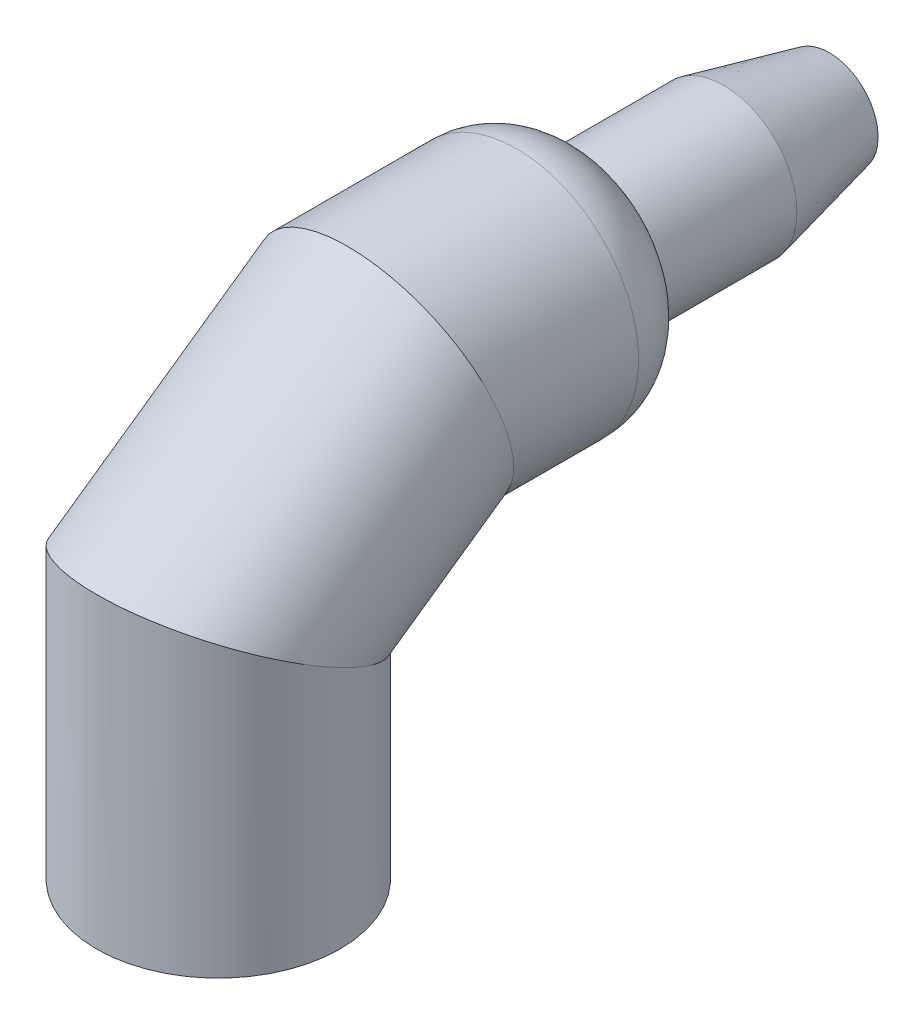
SolidWorks part; units mm, degrees
material "ABS"
ref_plane "Front Plane" through (0, 0, 0) normal (0, 0, 1) x (1, 0, 0)
ref_plane "Top Plane" through (0, 0, 0) normal (0, 1, 0) x (1, 0, 0)
ref_plane "Right Plane" through (0, 0, 0) normal (1, 0, 0) x (0, 0, -1)
sketch "Sketch1" plane through (0, 0, 0) normal (0, 1, 0) x (1, 0, 0)
  circle A0 centre (0, 0) radius 4.1
  circle A1 centre (0, 0) radius 5.1
  dimension "D1" = 8.2
  dimension "D2" = 1
sketch "Sketch2" plane through (0, 0, 0) normal (1, 0, 0) x (0, 0, -1)
  line L0 (5.1, 5) -> (7.4382, 6.6372)
  line L1 (-5.1, 5) -> (-1.6582, 7.41)
  line L3 (-1.6582, 7.41) -> (7.4382, 7.41)
  line L4 (7.4382, 6.6372) -> (7.4382, 7.41) construction
  line L6 (5.1, 0) -> (-5.1, 0) construction
  line L7 (5.1, 0) -> (-5.1, 0) construction
  line L8 (-5.1, 0) -> (-5.1, 5)
  line L9 (5.1, 0) -> (5.1, 5)
  dimension "D1" = 5
  dimension "D2" = 5
sweep "Sweep4" add path "Sketch2" circular profile diameter 5 parameters "D3"=5
shell "Shell1" thickness 1 removed face at (2.5, 7.41, -7.4382) removed face at (2.5, 0, 5.1)
sketch "Sketch15" plane through (0, 0, -7.4382) normal (0, 0, -1) x (-1, 0, 0)
  circle A1 centre (0, 7.41) radius 1
  dimension "D3" = 2
ref_plane "Plane1" through (0, 0, -0.9382) normal (0, 0, -1) x (-1, 0, 0)
sketch "Sketch16" plane through (0, 0, -0.9382) normal (0, 0, -1) x (-1, 0, 0)
  circle A0 centre (0, 7.41) radius 2.5
  circle A1 centre (0, 7.41) radius 2.5 construction
loft "Loft2" add profiles "Sketch15", "Sketch16" connector at (-1, 7.41, -7.4382) connector at (-2.5, 7.41, -0.9382)
sketch "Sketch17" plane through (0, 0, -7.4382) normal (0, 0, -1) x (-1, 0, 0)
  circle A0 centre (0, 7.41) radius 1.5 construction
  circle A1 centre (0, 7.41) radius 2.5
  circle A2 centre (0, 7.41) radius 2.5
  circle A3 centre (0, 7.41) radius 1.5
  dimension "D1" = 0
extrude "Cut-Extrude1" cut sketch "Sketch17" against normal blind 5
sketch "Sketch20" plane through (0, 0, -7.4382) normal (0, 0, -1) x (-1, 0, 0)
  circle A0 centre (0, 7.41) radius 0.5
  dimension "D1" = 1
sketch "Sketch21" plane through (0, 0, -0.9382) normal (0, 0, 1) x (1, 0, 0)
  circle A0 centre (0, 7.41) radius 1
  circle A1 centre (0, 7.41) radius 1.5
  circle A2 centre (0, 7.41) radius 1.5 construction
  dimension "D2" = 0.5
  dimension "D1" = 0
loft "Cut-Loft1" cut profiles "Sketch20", "Sketch21" connector at (-0.5, 7.41, -7.4382) connector at (-0.9718, 7.6459, -0.9382)
fillet "Fillet2" radius 1.5 1 edges at (1, 7.41, -0.9382)
fillet "Fillet3" radius 1.5 1 edges at (-2.5, 7.41, -2.4382)
sketch "Sketch24" plane through (0, 0, 0) normal (1, 0, 0) x (0, 0, -1)
  line L0 (-2.6, 0) -> (-2.6, 3.6986)
  line L1 (-2.6, 3.6986) -> (-0.87, 4.91)
  line L2 (-0.87, 4.91) -> (1.0239, 4.91)
  line L3 (2.4382, 8.91) -> (2.4382, 5.91) construction
  line L4 (2.4382, 5.91) -> (5.2715, 5.91)
  line L5 (5.2715, 5.91) -> (7.4382, 6.41)
  line L6 (7.4382, 6.41) -> (7.4382, 6.91)
  line L7 (7.4382, 6.41) -> (7.4382, 8.41) construction
  line L8 (-7.6, 0) -> (-7.6, 6.3014)
  line L9 (-7.6, 6.3014) -> (-2.4465, 9.91)
  line L10 (-2.4465, 9.91) -> (1.0239, 9.91)
  line L11 (1.0239, 9.91) -> (-2.4465, 9.91) construction
  line L13 (2.4382, 8.91) -> (5.2715, 8.91)
  line L14 (5.2715, 8.91) -> (7.4382, 8.41)
  line L15 (7.4382, 8.41) -> (7.4382, 6.91)
  arc A0 (1.0239, 4.91) -> (2.4382, 5.91) centre (1.0239, 6.41) ccw
  arc A1 (1.0239, 4.91) -> (2.4382, 5.91) centre (1.0239, 6.41) ccw construction
  arc A2 (2.4382, 8.91) -> (1.0239, 9.91) centre (1.0239, 8.41) ccw construction
  arc A3 (1.0239, 9.91) -> (2.4382, 8.91) centre (1.0239, 8.41) cw
  dimension "D1" = 0.5
fillet "Fillet4" radius 2.5 1 edges at (0, 0, 3.6)
